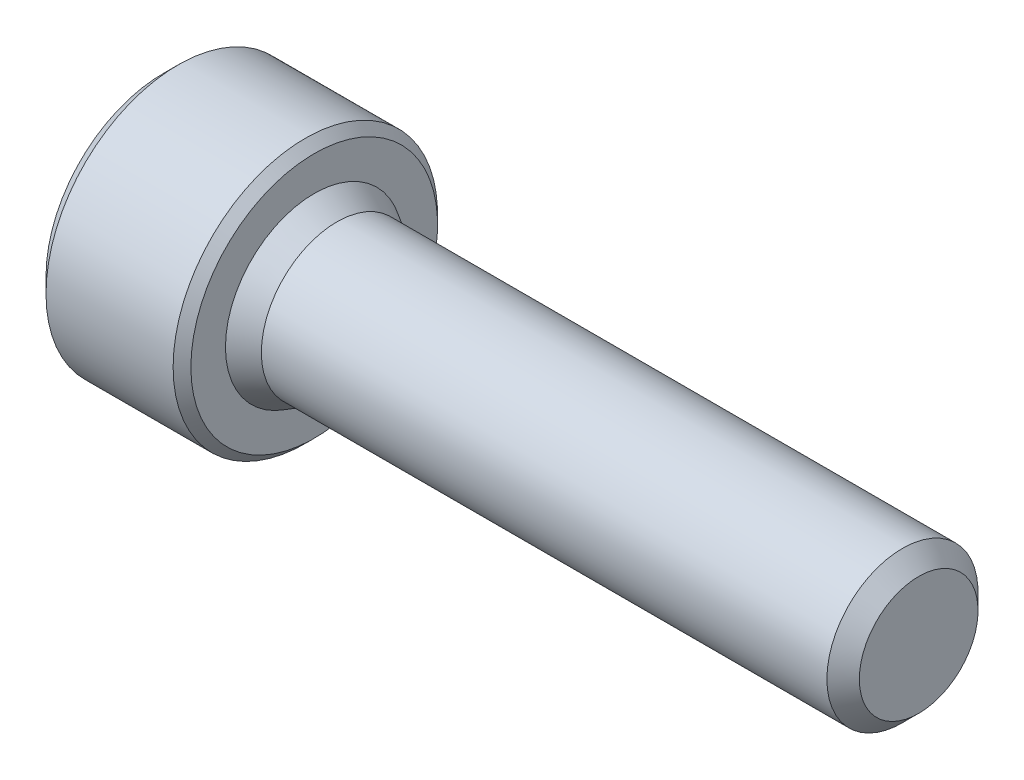
SolidWorks part; units mm, degrees
ref_plane "Front Plane" through (0, 0, 0) normal (0, 0, 1) x (1, 0, 0)
ref_plane "Top Plane" through (0, 0, 0) normal (0, 1, 0) x (1, 0, 0)
ref_plane "Right Plane" through (0, 0, 0) normal (1, 0, 0) x (0, 0, -1)
sketch "Sketch1" plane through (0, 0, 0) normal (0, 0, 1) x (1, 0, 0)
  line L0 (-4, 0) -> (-4, 3.5)
  line L1 (-4, 3.5) -> (0, 3.5)
  line L2 (0, 3.5) -> (0, 2.35)
  line L3 (0, 2.35) -> (0.6, 2)
  line L4 (0.6, 2) -> (15.5705, 2)
  line L5 (15.5705, 2) -> (16, 1.5705)
  line L6 (16, 1.5705) -> (16, 0)
  line L7 (16, 0) -> (-4, 0)
  line L8 (16, 0) -> (-4, 0) construction
revolve "Revolve1" add sketch "Sketch1" angle 360 about L8 reverse direction yes
cosmetic thread "Cosmetic Thread1" parameters "D1"=13.9, "D2"=3.141
sketch "Sketch2" plane through (0, 0, 0) normal (0, 0, 1) x (1, 0, 0)
  line L0 (-4, 3.1) -> (-3.6, 3.5)
  line L1 (-3.6, 3.5) -> (-0.235, 3.5)
  line L2 (-0.235, 3.5) -> (0, 3.265)
  line L3 (0, 3.265) -> (0, 4.2)
  line L4 (0, 4.2) -> (-4, 4.2)
  line L5 (-4, 4.2) -> (-4, 3.1)
  line L6 (0, 0) -> (-4, 0) construction
revolve "Cut-Revolve1" cut sketch "Sketch2" angle 360 about L6 reverse direction yes
sketch "Sketch3" plane through (0, 0, 0) normal (0, 0, 1) x (1, 0, 0)
  line L0 (-4, 0) -> (-4, 1.71)
  line L1 (-4, 1.71) -> (-3.79, 1.5)
  line L2 (-3.79, 1.5) -> (-2, 1.5)
  line L3 (-2, 1.5) -> (-1.134, 0)
  line L4 (-1.134, 0) -> (-4, 0)
  line L5 (-1.134, 0) -> (-4, 0) construction
revolve "Cut-Revolve2" cut sketch "Sketch3" angle 360 about L5 reverse direction yes
ref_plane "Plane1" through (-4, 0, 0) normal (1, 0, 0) x (0, 0, -1)
sketch "Sketch4" plane through (-4, 0, 0) normal (1, 0, 0) x (0, 0, -1)
  line L0 (-1.5, -0.866) -> (0, -1.7321)
  line L1 (0, -1.7321) -> (1.5, -0.866)
  line L2 (1.5, -0.866) -> (1.5, 0.866)
  line L3 (1.5, 0.866) -> (0, 1.7321)
  line L4 (0, 1.7321) -> (-1.5, 0.866)
  line L5 (-1.5, 0.866) -> (-1.5, -0.866)
extrude "Cut-Extrude1" cut sketch "Sketch4" along normal blind 2 and the other way blind 2
ref_plane "Plane2" through (-4, 0, 0) normal (1, 0, 0) x (0, 0, -1)
ref_plane "Plane3" through (16, 0, 0) normal (1, 0, 0) x (0, 0, -1)
ref_plane "Plane4" through (0, 0, 0) normal (1, 0, 0) x (0, 0, -1)
ref_plane "ANBAU XY" through (0, 0, 0) normal (-1, 0, 0) x (0, 0, 1)
ref_plane "ANBAU XZ" through (0, 0, 0) normal (0, 1, 0) x (1, 0, 0)
ref_plane "ANBAU YZ" through (0, 0, 0) normal (0, 0, -1) x (-1, 0, 0)
ref_axis "ANBAU X" through (0, 0, 80.9) along (0, 0, -1)
ref_axis "ANBAU Y" through (0, 50, 0) along (0, -1, 0)
ref_axis "ANBAU Z" through (-80.9, 0, 0) along (1, 0, 0)
sketch3d "ANBAU"
  point P0 (0, 0, 0)
ref_plane "IP1 XY" through (0, 0, 0) normal (1, 0, 0) x (0, 0, -1)
ref_plane "IP1 XZ" through (0, 0, 0) normal (0, -1, 0) x (-1, 0, 0)
ref_plane "IP1 YZ" through (0, 0, 0) normal (0, 0, -1) x (-1, 0, 0)
ref_axis "IP1 X" through (0, 0, 80.9) along (0, 0, -1)
ref_axis "IP1 Y" through (0, -50, 0) along (0, 1, 0)
ref_axis "IP1 Z" through (80.9, 0, 0) along (-1, 0, 0)
sketch3d "IP1"
  point P0 (0, 0, 0)
ref_plane "IP2 XY" through (-4, 0, 0) normal (1, 0, 0) x (0, 0, -1)
ref_plane "IP2 XZ" through (0, 0, 0) normal (0, -1, 0) x (-1, 0, 0)
ref_plane "IP2 YZ" through (0, 0, 0) normal (0, 0, -1) x (-1, 0, 0)
ref_axis "IP2 X" through (-4, 0, 80.9) along (0, 0, -1)
ref_axis "IP2 Y" through (-4, -50, 0) along (0, 1, 0)
ref_axis "IP2 Z" through (80.9, 0, 0) along (-1, 0, 0)
sketch3d "IP2"
  point P0 (-4, 0, 0)
ref_plane "IP3 XY" through (16, 0, 0) normal (1, 0, 0) x (0, 0, -1)
ref_plane "IP3 XZ" through (0, 0, 0) normal (0, -1, 0) x (-1, 0, 0)
ref_plane "IP3 YZ" through (0, 0, 0) normal (0, 0, -1) x (-1, 0, 0)
ref_axis "IP3 X" through (16, 0, 80.9) along (0, 0, -1)
ref_axis "IP3 Y" through (16, -50, 0) along (0, 1, 0)
ref_axis "IP3 Z" through (80.9, 0, 0) along (-1, 0, 0)
sketch3d "IP3"
  point P0 (16, 0, 0)
other "Freeze***"
